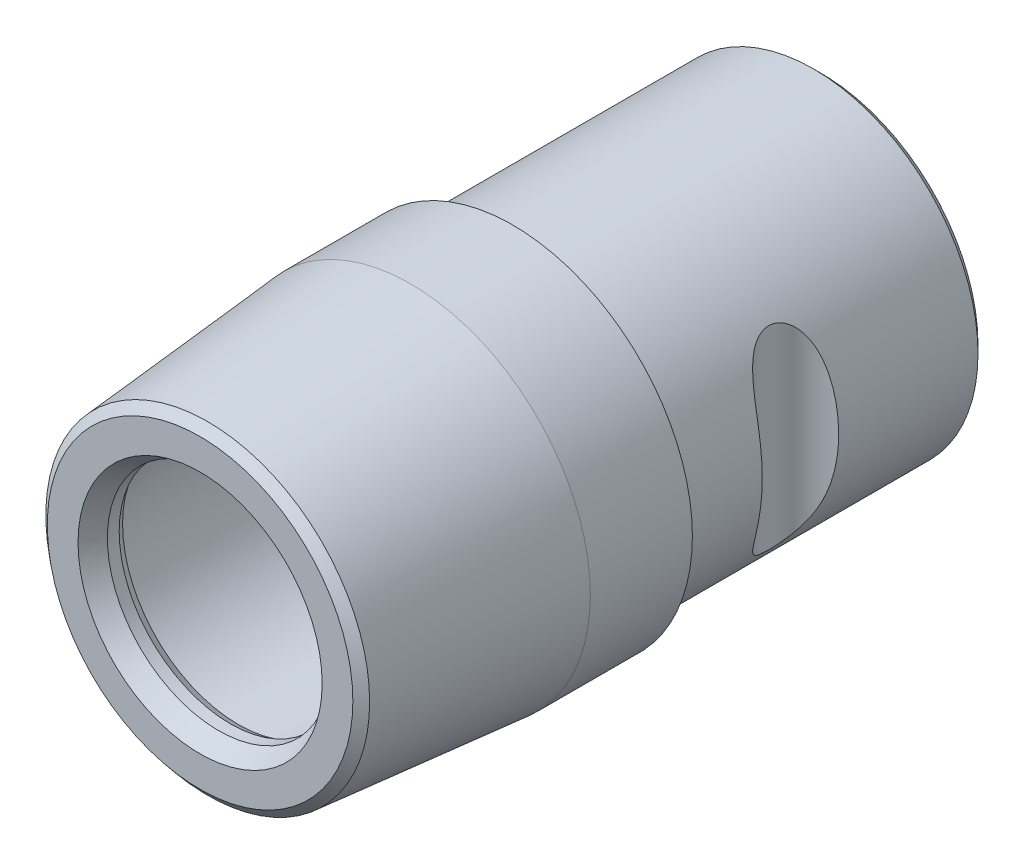
SolidWorks part; units mm, degrees
ref_plane "Front Plane" through (0, 0, 0) normal (0, 0, 1) x (1, 0, 0)
ref_plane "Top Plane" through (0, 0, 0) normal (0, 1, 0) x (1, 0, 0)
ref_plane "Right Plane" through (0, 0, 0) normal (1, 0, 0) x (0, 0, -1)
ref_axis "Axis X" through (-88.99, 0, 0) along (1, 0, 0)
ref_axis "Axis Y" through (0, 55, 0) along (0, -1, 0)
ref_axis "Axis Z" through (0, 0, -88.99) along (0, 0, 1)
sketch "Sketch1" plane through (0, 0, 0) normal (0, 1, 0) x (1, 0, 0)
  line L0 (10.7, 0) -> (10.7, -20.1)
  line L2 (11.7, -40.4625) -> (7.25, -40.4625)
  line L4 (7.25, -40.4625) -> (7.25, -37.9625)
  line L5 (7.25, -37.9625) -> (8.25, -37.9625)
  line L6 (8.25, -37.9625) -> (8.25, -27.8225)
  line L7 (8.25, 0) -> (10.7, 0)
  line L8 (0, -37.4625) -> (0, 0) construction
  line L9 (-10.3329, -37.4625) -> (49989.6671, -37.4625) construction
  line L10 (-7.0193, -20) -> (-50007.0193, -20) construction
  line L11 (-4.4082, -12.0625) -> (-50004.4082, -12.0625) construction
  line L12 (8.94, -27.8225) -> (8.25, -27.8225)
  line L13 (9.4774, -26.5251) -> (8.25, -25.2977)
  line L14 (8.94, -4.8225) -> (8.25, -4.8225)
  line L15 (9.4774, -3.5251) -> (8.25, -2.2977)
  line L16 (8.25, -25.2977) -> (8.25, -4.8225)
  line L17 (8.25, -2.2977) -> (8.25, 0)
  line L18 (10.7, -20.1) -> (11.7, -20.1)
  line L19 (11.7, -20.1) -> (11.7, -40.4625)
  circle A0 centre (11.166, -12.0625) radius 2.4312 construction
  arc A1 (8.94, -27.8225) -> (9.4774, -26.5251) centre (8.94, -27.0625) ccw
  arc A2 (8.94, -4.8225) -> (9.4774, -3.5251) centre (8.94, -4.0625) ccw
  dimension "D6" = 4.8625
  dimension "D9" = 1.52
  dimension "D1" = 21.4
  dimension "D2" = 17.4625
  dimension "D3" = 0.5
  dimension "D4" = 7.9375
  dimension "D5" = 16.5
  dimension "D7" = 11.166
  dimension "D8" = 20
  dimension "D10" = 17.88
  dimension "D11" = 45
  dimension "D12" = 8
  dimension "D13" = 15
  dimension "D14" = 1
  dimension "D15" = 14.5
  dimension "D16" = 2.5
  dimension "D17" = 0.1
revolve "Revolve1" add sketch "Sketch1" angle 360 about L8
chamfer "Chamfer1" distance 0.3 angle 60 1 edges at (7.25, 0, 37.9625) first distance on face at (7.25, 0, 37.9625)
chamfer "Chamfer3" distance 1.2 angle 85 1 edges at (11.7, 0, 40.4625) first distance on face at (11.7, 0, 40.4625)
chamfer "Chamfer2" distance 0.7 angle 60 1 edges at (7.25, 0, 40.4625) first distance on face at (10.5, 0, 40.4625)
sketch "Sketch3" plane through (0, 0, 0) normal (0, 1, 0) x (1, 0, 0)
  circle A0 centre (11.166, -12.0625) radius 2.4312 construction
  circle A1 centre (11.166, -12.0625) radius 2.4313 construction
  circle A2 centre (11.166, -12.0625) radius 2.5312
  dimension "D1" = 0.1
extrude "Cut-Extrude1" cut sketch "Sketch3" against normal through all both and the other way through all
chamfer "Chamfer4" distance 0.5 angle 45 2 edges at (10.7, 0, 0) (8.25, 0, 0)
chamfer "Chamfer5" distance 0.5 angle 45 1 edges at (10.5, 0, 40.4625) first distance on face at (11.7, 0, 26.7464)
